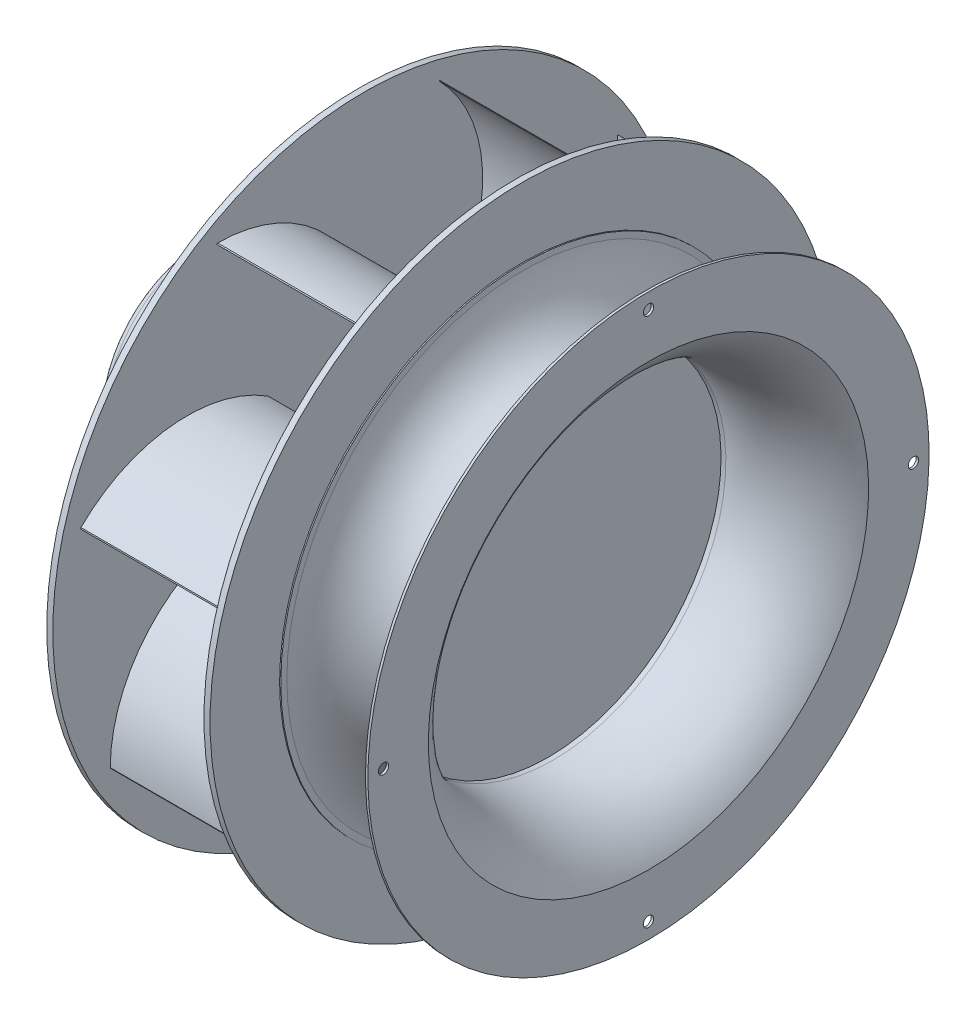
SolidWorks part; units mm, degrees
ref_plane "Front Plane" through (0, 0, 0) normal (0, 0, 1) x (1, 0, 0)
ref_plane "Top Plane" through (0, 0, 0) normal (0, 1, 0) x (1, 0, 0)
ref_plane "Right Plane" through (0, 0, 0) normal (1, 0, 0) x (0, 0, -1)
sketch "Sketch1" plane through (0, 0, 0) normal (0, 0, 1) x (1, 0, 0)
  line L0 (0, 0) -> (831.9083, 0) construction
  line L1 (0, 0) -> (0, 79.5)
  line L2 (5, 84.5) -> (70, 84.5)
  line L3 (70, 84.5) -> (70, 108.5)
  line L4 (70, 108.5) -> (90, 108.5)
  line L5 (90, 108.5) -> (90, 68.5)
  line L6 (90, 68.5) -> (95, 68.5)
  line L7 (95, 68.5) -> (95, 103.5)
  line L8 (95, 103.5) -> (105, 103.5)
  line L9 (105, 103.5) -> (105, 68.5)
  line L10 (105, 68.5) -> (130, 68.5)
  line L11 (130, 68.5) -> (130, 0)
  line L12 (130, 0) -> (0, 0)
  arc A0 (5, 84.5) -> (0, 79.5) centre (5, 79.5) ccw
  point P16 (0, 84.5)
  dimension "D10" = 5
  dimension "D1" = 84.5
  dimension "D2" = 24
  dimension "D3" = 70
  dimension "D4" = 40
  dimension "D5" = 35
  dimension "D6" = 5
  dimension "D7" = 20
  dimension "D8" = 10
  dimension "D9" = 60
revolve "Revolve1" add sketch "Sketch1" angle 360 about L0
sketch "Sketch2" plane through (130, 0, 0) normal (1, 0, 0) x (0, 0, -1)
  circle A0 centre (0, 0) radius 257.5
  dimension "D1" = 515
extrude "Extrude1" add sketch "Sketch2" along normal blind 5
sketch "Sketch9" plane through (130, 0, 0) normal (-1, 0, 0) x (0, 0, 1)
  circle A0 centre (0, 0) radius 252.5
  circle A1 centre (0, 0) radius 100
  circle A2 centre (0, 0) radius 257.5 construction
  dimension "D1" = 5
  dimension "D2" = 200
extrude "Extrude7" cut sketch "Sketch9" against normal blind 3
ref_plane "Plane1" through (260, 0, 0) normal (1, 0, 0) x (0, 0, -1)
sketch "Sketch3" plane through (260, 0, 0) normal (1, 0, 0) x (0, 0, -1)
  circle A0 centre (0, 0) radius 257.5
  dimension "D1" = 515
extrude "Extrude2" add sketch "Sketch3" along normal blind 5 separate body
sketch "Sketch4" plane through (135, 0, 0) normal (1, 0, 0) x (0, 0, -1)
  line L0 (0, 0) -> (0, 242.5) construction
  line L1 (0, 0) -> (128.75, 223.0015) construction
  line L2 (0, 112.5) -> (0.866, 112) construction
  line L3 (121.25, 210.0112) -> (122.116, 209.5112) construction
  line L4 (-121.25, 210.0112) -> (-122.116, 209.5112)
  line L5 (0, 112.5) -> (-0.866, 112)
  circle A0 centre (0, 0) radius 242.5 construction
  circle A1 centre (0, 0) radius 257.5 construction
  circle A2 centre (0, 0) radius 112.5 construction
  arc A3 (0, 112.5) -> (121.25, 210.0112) centre (121.9404, 85.0131) cw construction
  arc A4 (0.866, 112) -> (122.116, 209.5112) centre (122.8065, 84.5131) cw construction
  arc A5 (0, 112.5) -> (-121.25, 210.0112) centre (-121.9404, 85.0131) ccw
  arc A6 (-0.866, 112) -> (-122.116, 209.5112) centre (-122.8065, 84.5131) ccw
  dimension "D1" = 15
  dimension "D2" = 225
  dimension "D6" = 125
  dimension "D7" = 125
  dimension "D3" = 30
  dimension "D4" = 60
  dimension "D5" = 1
extrude "Extrude3" add sketch "Sketch4" along normal up to surface (130 mm away) up to face at (265, 0, -257.5)
ref_axis "Axis1" through (253.5503, 0, 0) along (-1, 0, 0)
pattern_circular "CirPattern1" count 8 over 360 about axis through (253.5503, 0, 0) along (-1, 0, 0) of "Extrude3"
sketch "Sketch5" plane through (0, 0, 0) normal (0, 0, 1) x (1, 0, 0)
  line L0 (0, 0) -> (527.2916, 0) construction
  line L1 (253.5503, 0) -> (75.411, 0) construction
  line L2 (265, 200) -> (266, 200)
  line L3 (266, 200) -> (266, 195)
  line L4 (265, 200) -> (265, 195)
  line L5 (309, 146) -> (309, 145)
  line L6 (70, 108.5) -> (70, -108.5) construction
  line L7 (265, -257.5) -> (265, 257.5) construction
  arc A0 (266, 195) -> (309, 146) centre (325.3621, 203.7259) ccw
  arc A1 (265, 195) -> (309, 145) centre (324.4681, 202.9719) ccw
  dimension "D7" = 60
  dimension "D8" = 60
  dimension "D1" = 145
  dimension "D2" = 1
  dimension "D3" = 1
  dimension "D4" = 5
  dimension "D5" = 200
  dimension "D6" = 239
revolve "Revolve2" add sketch "Sketch5" angle 360 about L0
ref_plane "Plane3" through (370, 0, 0) normal (1, 0, 0) x (0, 0, -1)
sketch "Sketch6" plane through (0, 0, 0) normal (0, 0, 1) x (1, 0, 0)
  line L0 (370, 232) -> (368, 232)
  line L1 (370, -251.35) -> (370, 251.35) construction
  line L2 (368, 232) -> (368, 182)
  line L3 (0, 0) -> (615.1417, 0) construction
  line L4 (0, 84.5) -> (0, -84.5) construction
  line L5 (253.5503, 0) -> (75.411, 0) construction
  line L6 (370, 232) -> (370, 182)
  line L7 (287, 145) -> (291, 145)
  line L8 (287, 145) -> (287, 143)
  line L9 (287, 143) -> (291, 143)
  arc A0 (291, 145) -> (368, 182) centre (300.2033, 224.4689) ccw
  arc A1 (291, 143) -> (370, 182) centre (300.9389, 222.3802) ccw
  dimension "D7" = 80
  dimension "D8" = 80
  dimension "D1" = 232
  dimension "D2" = 2
  dimension "D3" = 182
  dimension "D4" = 83
  dimension "D5" = 145
  dimension "D6" = 4
revolve "Revolve3" add sketch "Sketch6" angle 360 about L3
sketch "Sketch7" plane through (370, 0, 0) normal (1, 0, 0) x (0, 0, -1)
  line L0 (0, 0) -> (0, 219) construction
  circle A0 centre (0, 0) radius 219 construction
  circle A1 centre (0, 219) radius 4.25
  dimension "D1" = 438
  dimension "D2" = 8.5
extrude "Extrude5" cut sketch "Sketch7" against normal blind 5
pattern_circular "CirPattern2" count 4 over 360 about axis through (253.5503, 0, 0) along (-1, 0, 0) of "Extrude5"
sketch "Sketch8" plane through (0, 0, 0) normal (1, 0, 0) x (0, 0, -1)
  line L0 (0, 0) -> (0, 95) construction
  circle A0 centre (0, 0) radius 95 construction
  circle A1 centre (0, 95) radius 5
  dimension "D1" = 190
  dimension "D2" = 10
extrude "Extrude6" cut sketch "Sketch8" along normal up to surface (90 mm away) up to face at (90, 0, 108.5)
pattern_circular "CirPattern3" count 8 over 360 about axis through (253.5503, 0, 0) along (-1, 0, 0) of "Extrude6"
